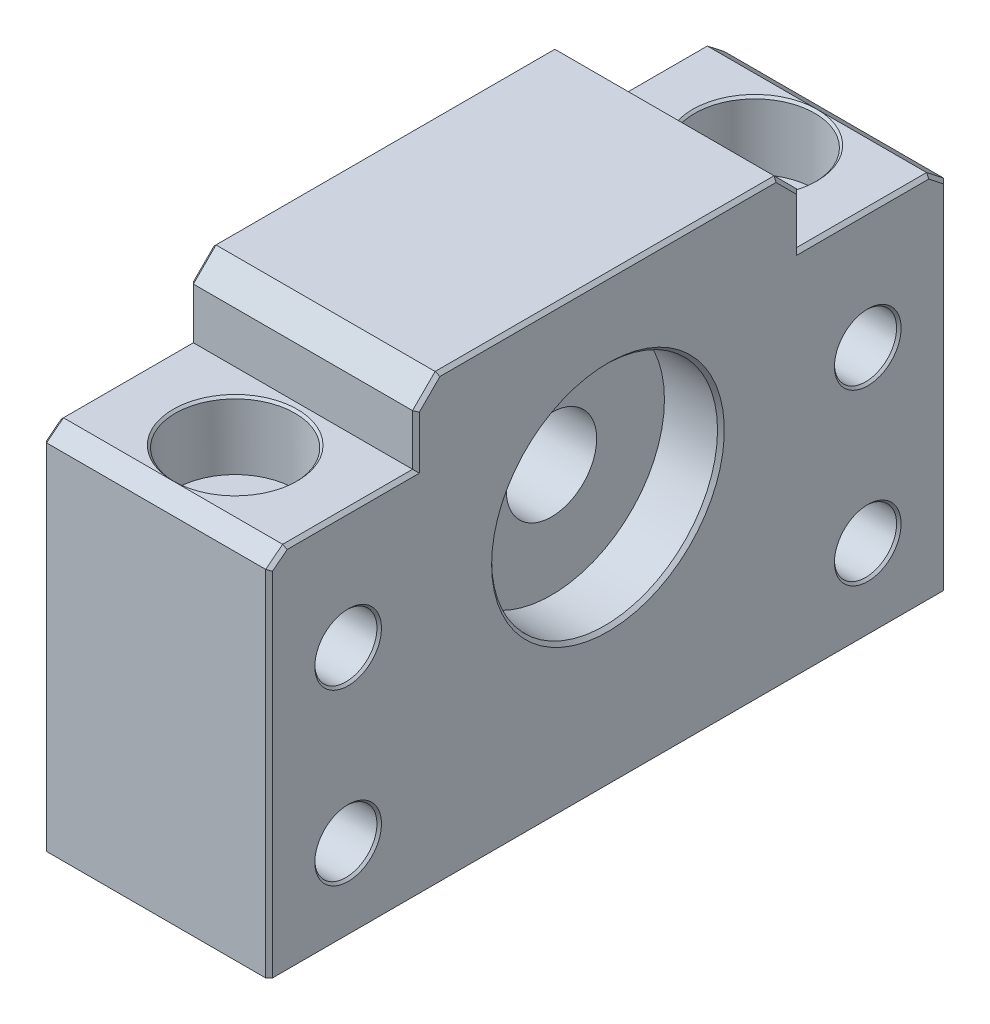
SolidWorks part; units mm, degrees
ref_plane "Front Plane" through (0, 0, 0) normal (0, 0, 1) x (1, 0, 0)
ref_plane "Top Plane" through (0, 0, 0) normal (0, 1, 0) x (1, 0, 0)
ref_plane "Right Plane" through (0, 0, 0) normal (1, 0, 0) x (0, 0, -1)
sketch "Sketch1" plane through (0, 0, 0) normal (1, 0, 0) x (0, 0, -1)
  line L0 (-30, -22) -> (30, -22)
  line L1 (-17, 15) -> (-15, 17)
  line L2 (15, 17) -> (17, 15)
  line L4 (-15, 17) -> (15, 17)
  line L6 (-17, 15) -> (-17, 10.5)
  line L12 (17, 10.5) -> (17, 15)
  line L17 (28.5, 10.5) -> (30, 9.3281)
  line L19 (30, 9.3281) -> (30, -22)
  line L20 (-30, 9.3277) -> (-28.5, 10.4997)
  line L21 (-30, -22) -> (-30, 9.3277)
  line L23 (-28.5, 10.4997) -> (-17, 10.5)
  line L24 (17, 10.5) -> (28.5, 10.5)
  circle A0 centre (0, 0) radius 4
  circle A1 centre (0, 0) radius 10 construction
  circle A2 centre (-23, 0) radius 2.75
  circle A3 centre (23, 0) radius 2.75
  circle A4 centre (23, -15) radius 2.75
  circle A5 centre (-23, -15) radius 2.75
  point P4 (23, 0)
  point P7 (30, 10.5)
  point P10 (-30, -22)
  point P11 (30, -22)
  point P15 (17, 17)
  point P16 (-17, 17)
  point P17 (23, -15)
  point P18 (-23, -15)
  point P19 (-23, 0)
  point P20 (0, 0)
  point P25 (-30, 10.4997)
  point P26 (28.5, 10.5)
  point P30 (-28.5, 10.4997)
  point P31 (30, 10.5)
  point P32 (30, 9.3281)
  point P39 (-30, 9.3277)
  dimension "D1" = 8
  dimension "D2" = 20
  dimension "D8" = 5.5
  dimension "D3" = 39
  dimension "D4" = 1.5
  dimension "D5" = 22
  dimension "D6" = 15
  dimension "D7" = 34
  dimension "D9" = 38
  dimension "D10" = 1.5
  dimension "D11" = 38
  dimension "D12" = 60
  dimension "D13" = 11.5
extrude "Boss-Extrude1" add sketch "Sketch1" along normal blind 20
sketch "Sketch2" plane through (0, 0, 0) normal (-1, 0, 0) x (0, 0, 1)
  circle A0 centre (0, 0) radius 10
  dimension "D1" = 20
extrude "Cut-Extrude1" cut sketch "Sketch2" against normal blind 5
sketch "Sketch3" plane through (20, 0, 0) normal (1, 0, 0) x (0, 0, -1)
  circle A0 centre (0, 0) radius 10
  dimension "D1" = 20
extrude "Cut-Extrude2" cut sketch "Sketch3" against normal blind 5
chamfer "Chamfer2" distance 0.2 angle 45 1 edges at (0, 0, -25.75)
chamfer "Chamfer3" distance 0.2 angle 45 3 edges at (0, -15, 20.25) (0, 0, 20.25) (0, -15, -25.75)
chamfer "Chamfer4" distance 0.2 angle 45 4 edges at (20, -15, -25.75) (20, 0, -25.75) (20, -15, 20.25) (20, 0, 20.25)
sketch "Sketch4" plane through (0, -22, 0) normal (0, -1, 0) x (1, 0, 0)
  line L0 (10, 30) -> (10, -30) construction
  line L1 (20, 30) -> (0, 30) construction
  line L2 (20, -30) -> (0, -30) construction
  circle A0 centre (10, 23) radius 2.75
  circle A1 centre (10, -23) radius 2.75
  point P6 (10, 23)
  point P7 (10, -23)
  point P8 (10, 0)
  point P13 (10, -23)
  dimension "D3" = 5.5
  dimension "D1" = 23
  dimension "D2" = 23
extrude "Cut-Extrude4" cut sketch "Sketch4" against normal up to surface (32.5 mm away) and the other way through all up to face at (10, 10.5, -22.75)
sketch "Sketch5" plane through (0, 10.5, 0) normal (0, 1, 0) x (1, 0, 0)
  circle A0 centre (10, 23) radius 5.3
extrude "Cut-Extrude6" cut sketch "Sketch5" against normal blind 6
sketch "Sketch6" plane through (0, 10.5004, 0.0002) normal (0, 1, 0) x (1, 0, 0)
  line L0 (10, -23.0004) -> (10, -23.0005) construction
  circle A0 centre (10, -23.0004) radius 5.3
extrude "Cut-Extrude7" cut sketch "Sketch6" against normal blind 6 contours A0
chamfer "Chamfer6" distance 0.2 angle 45 1 edges at (10, 10.4997, 28.3006)
chamfer "Chamfer7" distance 0.2 angle 45 1 edges at (10, 10.5, -17.7)
chamfer "Chamfer11" distance 0.3 angle 45 12 edges at (20, 0, -10) (20, -6.336, -30) (20, 9.914, -29.25) (20, 10.5, -22.75) (20, 12.75, -17) (20, 16, -16) (20, -6.3361, 30) (20, 9.9137, 29.25) (20, 10.4999, 22.75) (20, 12.75, 17) (20, 16, 16) (20, 17, 0)
chamfer "Chamfer12" distance 0.3 angle 45 12 edges at (0, 0, 10) (0, -6.3361, 30) (0, 9.9137, 29.25) (0, 10.4999, 22.75) (0, 12.75, 17) (0, 16, 16) (0, 17, 0) (0, 16, -16) (0, 12.75, -17) (0, 10.5, -22.75) (0, 9.914, -29.25) (0, -6.336, -30)
